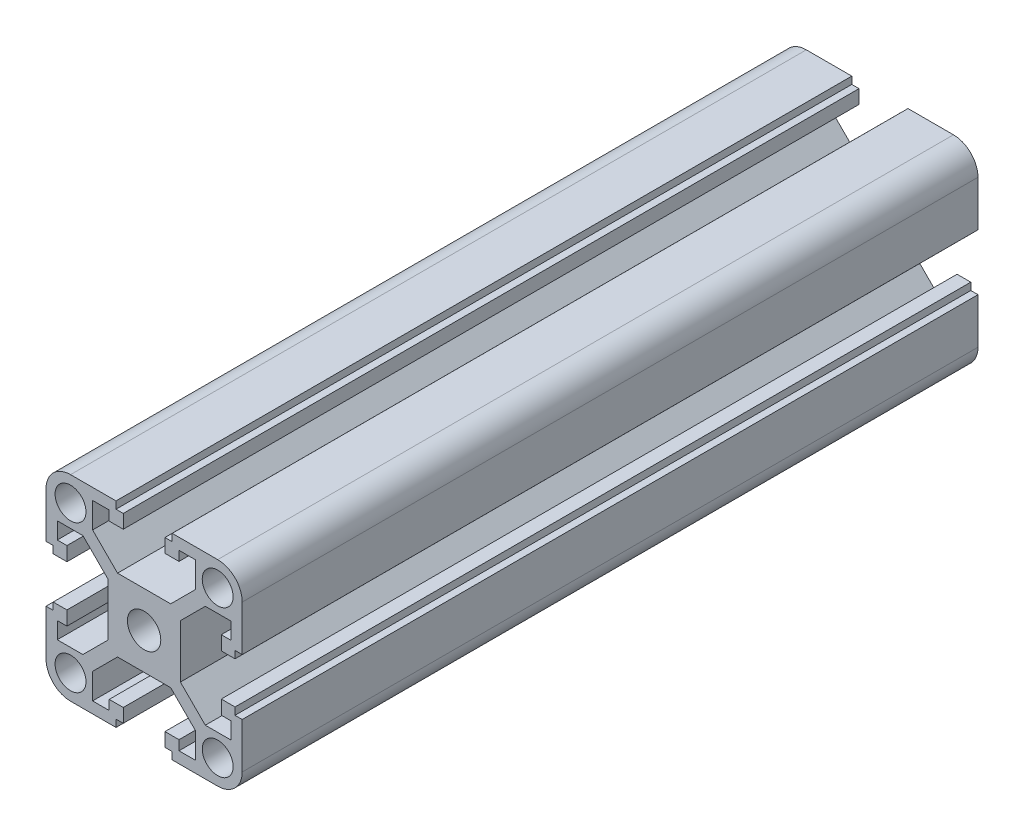
SolidWorks part; units mm, degrees
material "АД1 ГОСТ 4784-97"
ref_plane "Спереди" through (0, 0, 0) normal (0, 0, 1) x (1, 0, 0)
ref_plane "Сверху" through (0, 0, 0) normal (0, 1, 0) x (1, 0, 0)
ref_plane "Справа" through (0, 0, 0) normal (1, 0, 0) x (0, 0, -1)
ref_axis "ОсьX" through (-88.99, 0, 0) along (1, 0, 0)
ref_axis "ОсьZ" through (0, 55, 0) along (0, -1, 0)
ref_axis "ОсьY" through (0, 0, -88.99) along (0, 0, 1)
sketch "Эскиз1" plane through (0, 0, 0) normal (0, 0, 1) x (1, 0, 0)
  line L0 (-15, 20) -> (-5.7274, 20)
  line L1 (-5.7274, 20) -> (-5.7274, 18.5304)
  line L2 (-5.7274, 18.5304) -> (-4.25, 18.5304)
  line L3 (-4.25, 18.5304) -> (-4.25, 15.732)
  line L4 (-4.25, 15.732) -> (-7.1118, 15.732)
  line L5 (-7.1118, 15.732) -> (-7.1118, 17.7)
  line L6 (-7.1118, 17.7) -> (-10.5, 17.7)
  line L7 (-10.5, 17.7) -> (-10.5, 12.4799)
  line L8 (-10.5, 12.4799) -> (-5.4201, 7.4)
  line L9 (-20, 15) -> (-20, 5.7274)
  line L10 (0, 0) -> (0, 8.4096) construction
  line L11 (-15, 15) -> (0, 0) construction
  line L12 (10.5, 12.4799) -> (5.4201, 7.4)
  line L13 (10.5, 17.7) -> (10.5, 12.4799)
  line L14 (7.1118, 17.7) -> (10.5, 17.7)
  line L15 (7.1118, 15.732) -> (7.1118, 17.7)
  line L16 (4.25, 15.732) -> (7.1118, 15.732)
  line L17 (4.25, 18.5304) -> (4.25, 15.732)
  line L18 (5.7274, 18.5304) -> (4.25, 18.5304)
  line L19 (5.7274, 20) -> (5.7274, 18.5304)
  line L20 (15, 20) -> (5.7274, 20)
  line L21 (-5.4201, 7.4) -> (5.4201, 7.4)
  line L22 (-8.8445, 0) -> (0, 0) construction
  line L23 (-12.4799, 10.5) -> (-7.4, 5.4201)
  line L24 (-17.7, 10.5) -> (-12.4799, 10.5)
  line L25 (-17.7, 7.1118) -> (-17.7, 10.5)
  line L26 (-15.732, 7.1118) -> (-17.7, 7.1118)
  line L27 (-15.732, 4.25) -> (-15.732, 7.1118)
  line L28 (-18.5304, 4.25) -> (-15.732, 4.25)
  line L29 (-18.5304, 5.7274) -> (-18.5304, 4.25)
  line L30 (-20, 5.7274) -> (-18.5304, 5.7274)
  line L31 (18.5304, 5.7274) -> (18.5304, 4.25)
  line L32 (18.5304, 4.25) -> (15.732, 4.25)
  line L33 (15.732, 4.25) -> (15.732, 7.1118)
  line L34 (15.732, 7.1118) -> (17.7, 7.1118)
  line L35 (12.4799, 10.5) -> (7.4, 5.4201)
  line L36 (17.7, 10.5) -> (12.4799, 10.5)
  line L37 (17.7, 7.1118) -> (17.7, 10.5)
  line L38 (20, 5.7274) -> (18.5304, 5.7274)
  line L39 (20, 15) -> (20, 5.7274)
  line L40 (20, -15) -> (20, -5.7274)
  line L41 (20, -5.7274) -> (18.5304, -5.7274)
  line L42 (17.7, -7.1118) -> (17.7, -10.5)
  line L43 (17.7, -10.5) -> (12.4799, -10.5)
  line L44 (12.4799, -10.5) -> (7.4, -5.4201)
  line L45 (15.732, -7.1118) -> (17.7, -7.1118)
  line L46 (15.732, -4.25) -> (15.732, -7.1118)
  line L47 (18.5304, -4.25) -> (15.732, -4.25)
  line L48 (18.5304, -5.7274) -> (18.5304, -4.25)
  line L49 (-20, -5.7274) -> (-18.5304, -5.7274)
  line L50 (-18.5304, -5.7274) -> (-18.5304, -4.25)
  line L51 (-18.5304, -4.25) -> (-15.732, -4.25)
  line L52 (-15.732, -4.25) -> (-15.732, -7.1118)
  line L53 (-15.732, -7.1118) -> (-17.7, -7.1118)
  line L54 (-17.7, -7.1118) -> (-17.7, -10.5)
  line L55 (-17.7, -10.5) -> (-12.4799, -10.5)
  line L56 (-12.4799, -10.5) -> (-7.4, -5.4201)
  line L57 (-5.4201, -7.4) -> (5.4201, -7.4)
  line L58 (15, -20) -> (5.7274, -20)
  line L59 (5.7274, -20) -> (5.7274, -18.5304)
  line L60 (5.7274, -18.5304) -> (4.25, -18.5304)
  line L61 (4.25, -18.5304) -> (4.25, -15.732)
  line L62 (4.25, -15.732) -> (7.1118, -15.732)
  line L63 (7.1118, -15.732) -> (7.1118, -17.7)
  line L64 (7.1118, -17.7) -> (10.5, -17.7)
  line L65 (10.5, -17.7) -> (10.5, -12.4799)
  line L66 (10.5, -12.4799) -> (5.4201, -7.4)
  line L67 (-20, -15) -> (-20, -5.7274)
  line L68 (-10.5, -12.4799) -> (-5.4201, -7.4)
  line L69 (-10.5, -17.7) -> (-10.5, -12.4799)
  line L70 (-7.1118, -17.7) -> (-10.5, -17.7)
  line L71 (-7.1118, -15.732) -> (-7.1118, -17.7)
  line L72 (-4.25, -15.732) -> (-7.1118, -15.732)
  line L73 (-4.25, -18.5304) -> (-4.25, -15.732)
  line L74 (-5.7274, -18.5304) -> (-4.25, -18.5304)
  line L75 (-5.7274, -20) -> (-5.7274, -18.5304)
  line L76 (-15, -20) -> (-5.7274, -20)
  line L77 (-7.4, 5.4201) -> (-7.4, -5.4201)
  line L78 (7.4, 5.4201) -> (7.4, -5.4201)
  circle A0 centre (0, 0) radius 3.4
  circle A1 centre (-15, 15) radius 3.15
  arc A2 (-15, 20) -> (-20, 15) centre (-15, 15) ccw
  arc A3 (15, 20) -> (20, 15) centre (15, 15) cw
  circle A4 centre (15, 15) radius 3.15
  circle A5 centre (15, -15) radius 3.15
  arc A6 (15, -20) -> (20, -15) centre (15, -15) ccw
  arc A7 (-15, -20) -> (-20, -15) centre (-15, -15) cw
  circle A8 centre (-15, -15) radius 3.15
  dimension "D1" = 6.8
  dimension "D2" = 6.3
  dimension "D3" = 40
  dimension "D8" = 30
  dimension "D4" = 2.3
  dimension "D5" = 1.35
  dimension "D6" = 21
  dimension "D7" = 8.5
  dimension "D9" = 45
  dimension "D10" = 2.8
  dimension "D11" = 4
  dimension "D13" = 40
extrude "Бобышка-Вытянуть1" add sketch "Эскиз1" along normal mid plane 150
